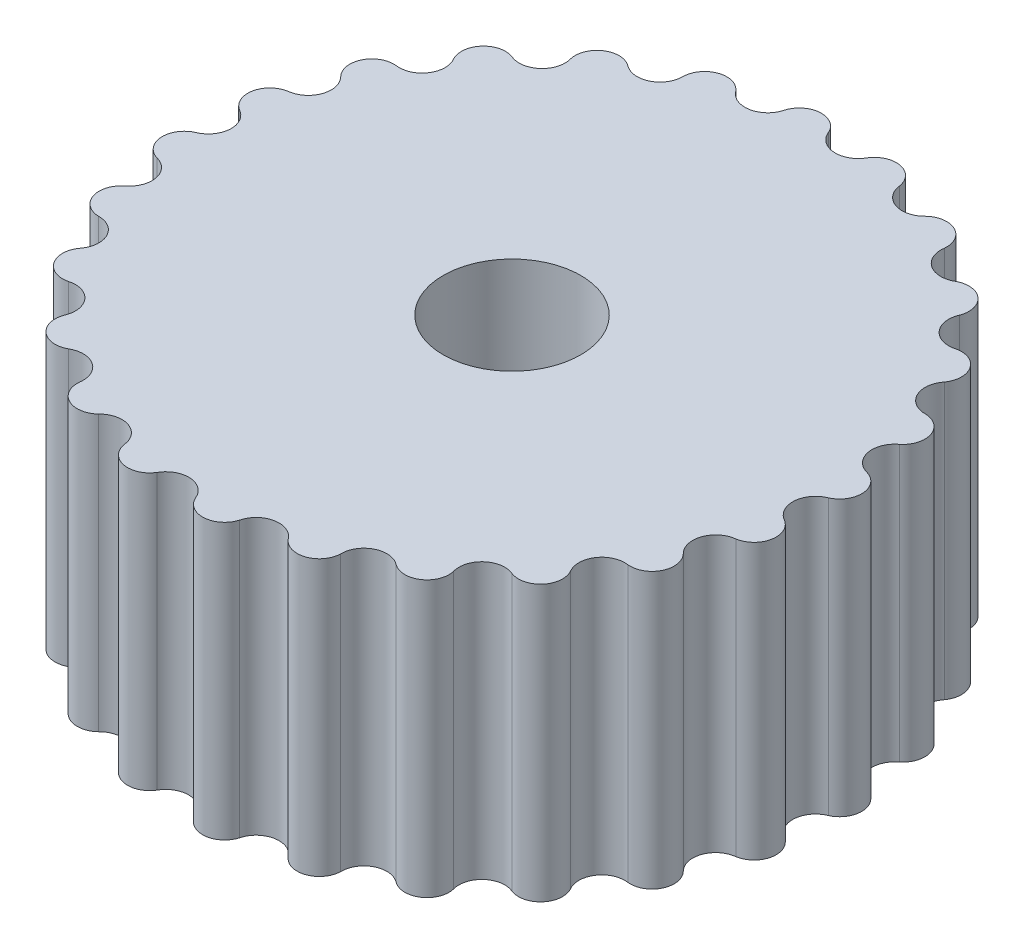
SolidWorks part; units mm, degrees
note: '?' marks a value the reader was unsure of.
ref_plane "Front Plane" through (0, 0, 0) normal (0, 0, 1) x (1, 0, 0)
ref_plane "Top Plane" through (0, 0, 0) normal (0, 1, 0) x (1, 0, 0)
ref_plane "Right Plane" through (0, 0, 0) normal (1, 0, 0) x (0, 0, -1)
sketch "Sketch1" plane through (0, 0, 0) normal (0, 1, 0) x (1, 0, 0)
  line L0 (0, 5.5) -> (0, 6) construction
  line L1 (0.7179, 5.4529) -> (0.7832, 5.9487) construction
  line L2 (1.4235, 5.3126) -> (1.5529, 5.7956) construction
  line L3 (0, 5.75) -> (0, 1.25)
  line L4 (0.3235, 1.2074) -> (1.4882, 5.5541)
  circle A0 centre (0, 0) radius 5.5 construction
  arc A1 (0, 5.75) -> (0.7505, 5.7008) centre (0.3869, 5.9037) ccw
  arc A2 (1.5529, 5.7956) -> (0, 6) centre (0, 0) ccw construction
  arc A3 (0.7505, 5.7008) -> (1.4882, 5.5541) centre (1.0924, 5.4917) cw
  arc A4 (0.3235, 1.2074) -> (0, 1.25) centre (0, 0) ccw
  point P6 (0, 5.75)
  point P9 (0.7505, 5.7008)
  dimension "D1" = 11
  dimension "D2" = 0.5
  dimension "D3" = 2.5
extrude "Boss-Extrude1" add sketch "Sketch1" along normal blind 5
pattern_circular "CirPattern1" count 24 over 360 about axis through (0, 0, 0) along (0, 1, 0) of "Boss-Extrude1"
ref_axis "Axis1" through (0, 0, 0) along (0, 1, 0)?
sketch "Sketch2" plane through (0, 5, 0) normal (0, 1, 0) x (1, 0, 0)
  line L0 (0, 74.1691) -> (0, -78.0459) construction
  line L1 (4.7625, 3.175) -> (6.6675, 3.175)
  line L2 (4.7625, 3.175) -> (4.7625, -3.175)
  line L3 (4.7625, -3.175) -> (6.6675, -3.175)
  line L4 (6.6675, 3.175) -> (6.6675, -3.175)
  line L5 (-6.6675, 3.175) -> (-6.6675, -3.175)
  line L6 (-4.7625, -3.175) -> (-6.6675, -3.175)
  line L7 (-4.7625, 3.175) -> (-4.7625, -3.175)
  line L8 (-4.7625, 3.175) -> (-6.6675, 3.175)
  point P6 (4.7625, 0)
  point P12 (-4.7625, 0)
  dimension "D1" = 1.905
  dimension "D2" = 6.35
  dimension "D3" = 4.7625
